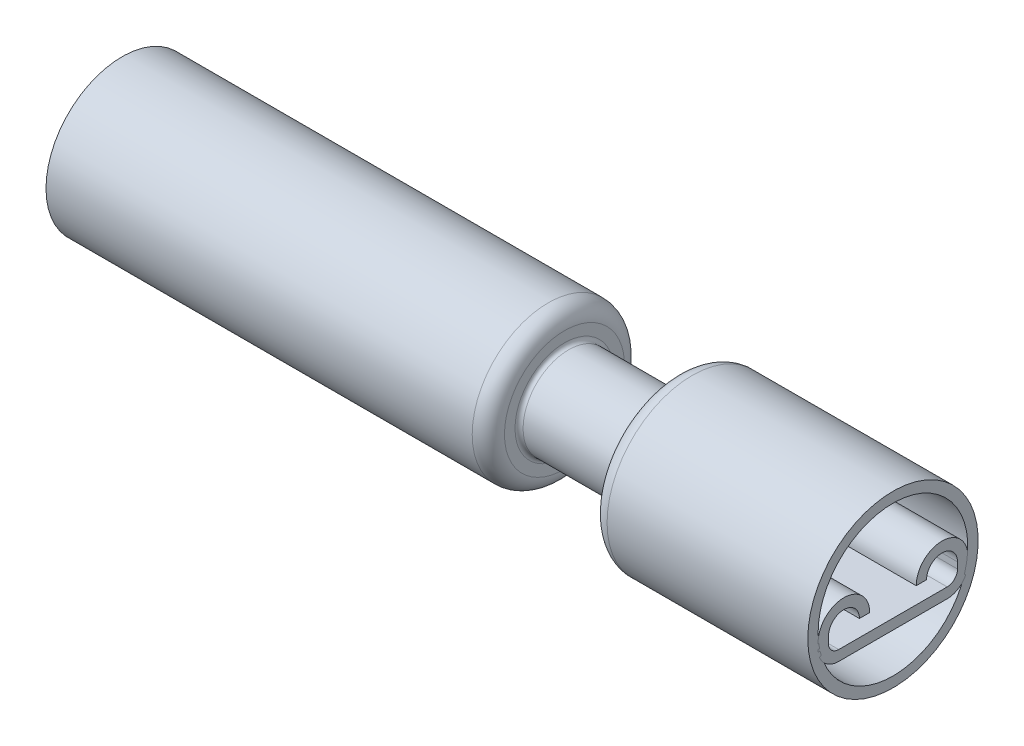
SolidWorks part; units mm, degrees
ref_plane "Front Plane" through (0, 0, 0) normal (0, 0, 1) x (1, 0, 0)
ref_plane "Top Plane" through (0, 0, 0) normal (0, 1, 0) x (1, 0, 0)
ref_plane "Right Plane" through (0, 0, 0) normal (1, 0, 0) x (0, 0, -1)
sketch "Sketch1" plane through (0, 0, 0) normal (1, 0, 0) x (0, 0, -1)
  line L0 (0, 3.2385) -> (0, -3.2385) construction
  line L1 (2.667, -1.7272) -> (-2.667, -1.7272) construction
  line L2 (-3.683, -0.7112) -> (-3.683, -0.4064) construction
  line L3 (-0.6096, 1.0559) -> (0, 0) construction
  line L4 (3.683, -0.7112) -> (3.683, -0.4064) construction
  line L5 (-3.175, -0.7112) -> (-3.175, -0.4064) construction
  line L6 (2.667, -1.2192) -> (-2.667, -1.2192) construction
  line L7 (3.175, -0.7112) -> (3.175, -0.4064) construction
  line L8 (-1.143, -0.4064) -> (-1.651, -0.4064) construction
  line L9 (1.143, -0.4064) -> (1.651, -0.4064) construction
  arc A0 (-3.683, -0.4064) -> (-1.143, -0.4064) centre (-2.413, -0.4064) cw construction
  arc A1 (-2.667, -1.7272) -> (-3.683, -0.7112) centre (-2.667, -0.7112) cw construction
  arc A2 (2.667, -1.7272) -> (3.683, -0.7112) centre (2.667, -0.7112) ccw construction
  arc A3 (3.683, -0.4064) -> (1.143, -0.4064) centre (2.413, -0.4064) ccw construction
  arc A4 (-3.175, -0.4064) -> (-1.651, -0.4064) centre (-2.413, -0.4064) cw construction
  arc A5 (-2.667, -1.2192) -> (-3.175, -0.7112) centre (-2.667, -0.7112) cw construction
  arc A6 (2.667, -1.2192) -> (3.175, -0.7112) centre (2.667, -0.7112) ccw construction
  arc A7 (3.175, -0.4064) -> (1.651, -0.4064) centre (2.413, -0.4064) ccw construction
  circle A8 centre (0, 0) radius 1.2192 construction
  point P4 (0, 0)
  point P14 (-0.6096, 1.0559)
  dimension "D2" = 1.016
  dimension "D3" = 1.27
  dimension "D4" = 2.4384
  dimension "Tubing ID" = 6.477
  dimension "Tab Width" = 6.35
  dimension "D5" = 30
  dimension "Tab Thickness" = 0.8128
  dimension "Thickness" = 0.508
sketch "Sketch2" plane through (0, 0, 0) normal (0, 0, 1) x (1, 0, 0)
  line L0 (18.9611, 0) -> (-18.9611, 0) construction
  point P4 (0, 0)
  dimension "Length" = 37.9222
sketch "Sketch3" plane through (0, 0, 0) normal (0, 1, 0) x (1, 0, 0)
  line L0 (8.8011, 0) -> (18.9611, 0) construction
  line L1 (18.9611, 0) -> (-18.9611, 0) construction
  line L2 (18.9611, -3.683) -> (18.9611, 3.683)
  line L3 (18.9611, 3.683) -> (11.0236, 3.683)
  line L4 (9.7358, 3.0238) -> (8.8011, 1.7272)
  line L5 (0, -1.2192) -> (0, 1.2192) construction
  line L6 (8.8011, 1.7272) -> (8.8011, -1.7272)
  line L7 (0, -1.2192) -> (0, 1.2192) construction
  line L8 (9.7358, -3.0238) -> (8.8011, -1.7272)
  line L9 (18.9611, -3.683) -> (11.0236, -3.683)
  arc A0 (11.0236, 3.683) -> (9.7358, 3.0238) centre (11.0236, 2.0955) ccw
  arc A1 (9.7358, -3.0238) -> (11.0236, -3.683) centre (11.0236, -2.0955) ccw
  point P21 (10.211, 3.683)
  point P24 (10.211, -3.683)
  dimension "D4" = 1.5875
  dimension "D1" = 10.16
  dimension "D2" = 0.508
  dimension "D3" = 7.9375
extrude "Boss-Extrude1" add sketch "Sketch3" along normal up to vertex (-0.4064 mm away) from vertex up to point (0, -0.4064, 3.683) starting at point (0, -1.7272, 2.667)
fillet "Fillet1" radius 1.016 6 edges at (14.9923, -1.7272, 3.683) (9.2685, -1.7272, 2.3755) (10.3003, -1.7272, 3.5086) (9.2685, -1.7272, -2.3755) (10.3003, -1.7272, -3.5086) (14.9923, -1.7272, -3.683)
shell "Shell1" thickness 0.508 removed face at (12.1105, -0.4064, 0) removed face at (18.9611, -1.0184, 0) removed face at (8.8011, -0.8758, 0)
sketch "Sketch4" plane through (8.8011, 0, 0) normal (-1, 0, 0) x (0, 0, 1)
  circle A0 centre (0, 0) radius 1.2192 construction
  circle A1 centre (0, 0) radius 1.2192
  circle A2 centre (0, 0) radius 1.7272
extrude "Boss-Extrude2" add sketch "Sketch4" along normal offset from surface (6.5087 mm away) 16.6687 up to face at (18.9611, -0.9162, 0)
sketch "Sketch5" plane through (2.2923, 0, 0) normal (-1, 0, 0) x (0, 0, 1)
  circle A0 centre (0, 0) radius 1.2192 construction
  circle A1 centre (0, 0) radius 1.2192
extrude "Cut-Extrude1" cut sketch "Sketch5" against normal through all
sketch "Sketch6" plane through (18.9611, 0, 0) normal (1, 0, 0) x (0, 0, -1)
  line L0 (-1.143, -0.4064) -> (-1.651, -0.4064) construction
  line L1 (-3.175, -0.7112) -> (-3.175, -0.4064) construction
  line L2 (2.667, -1.2192) -> (-2.667, -1.2192) construction
  line L3 (3.175, -0.7112) -> (3.175, -0.4064) construction
  line L4 (1.143, -0.4064) -> (1.651, -0.4064) construction
  line L5 (3.683, -0.7112) -> (3.683, -0.4064) construction
  line L6 (2.667, -1.7272) -> (-2.667, -1.7272) construction
  line L7 (-3.683, -0.7112) -> (-3.683, -0.4064) construction
  line L8 (3.683, -0.4064) -> (3.175, -0.4064)
  line L14 (-2.667, -1.7272) -> (2.667, -1.7272)
  line L16 (3.683, -0.4064) -> (3.175, -0.4064)
  line L22 (-2.667, -1.7272) -> (2.667, -1.7272)
  line L24 (-1.143, -0.4064) -> (-1.651, -0.4064)
  line L25 (-3.175, -0.7112) -> (-3.175, -0.4064)
  line L26 (2.667, -1.2192) -> (-2.667, -1.2192)
  line L27 (3.175, -0.7112) -> (3.175, -0.4064)
  line L28 (1.143, -0.4064) -> (1.651, -0.4064)
  line L29 (3.683, -0.7112) -> (3.683, -0.4064)
  line L30 (2.667, -1.7272) -> (-2.667, -1.7272)
  line L31 (-3.683, -0.7112) -> (-3.683, -0.4064)
  line L34 (3.175, -0.4064) -> (3.175, -0.7112)
  line L35 (3.175, -0.4064) -> (3.175, -0.7112)
  line L36 (2.667, -1.2192) -> (-2.667, -1.2192)
  line L37 (2.667, -1.2192) -> (-2.667, -1.2192)
  line L38 (-3.175, -0.7112) -> (-3.175, -0.4064)
  line L39 (-3.175, -0.7112) -> (-3.175, -0.4064)
  line L40 (-3.175, -0.4064) -> (-3.683, -0.4064)
  line L41 (-3.175, -0.4064) -> (-3.683, -0.4064)
  line L42 (-3.683, -0.4064) -> (-3.683, -0.7112)
  line L43 (-3.683, -0.4064) -> (-3.683, -0.7112)
  line L44 (3.683, -0.7112) -> (3.683, -0.4064)
  line L45 (3.683, -0.7112) -> (3.683, -0.4064)
  arc A0 (-1.143, -0.4064) -> (-3.683, -0.4064) centre (-2.413, -0.4064) ccw construction
  arc A1 (-1.651, -0.4064) -> (-3.175, -0.4064) centre (-2.413, -0.4064) ccw construction
  arc A2 (-3.175, -0.7112) -> (-2.667, -1.2192) centre (-2.667, -0.7112) ccw construction
  arc A3 (2.667, -1.2192) -> (3.175, -0.7112) centre (2.667, -0.7112) ccw construction
  arc A6 (-3.683, -0.7112) -> (-2.667, -1.7272) centre (-2.667, -0.7112) ccw
  arc A7 (2.667, -1.7272) -> (3.683, -0.7112) centre (2.667, -0.7112) ccw
  arc A10 (-3.683, -0.7112) -> (-2.667, -1.7272) centre (-2.667, -0.7112) ccw
  arc A11 (2.667, -1.7272) -> (3.683, -0.7112) centre (2.667, -0.7112) ccw
  arc A12 (3.175, -0.4064) -> (1.651, -0.4064) centre (2.413, -0.4064) ccw construction
  arc A13 (3.683, -0.4064) -> (1.143, -0.4064) centre (2.413, -0.4064) ccw construction
  arc A14 (2.667, -1.7272) -> (3.683, -0.7112) centre (2.667, -0.7112) ccw construction
  arc A15 (-3.683, -0.7112) -> (-2.667, -1.7272) centre (-2.667, -0.7112) ccw construction
  arc A16 (-1.143, -0.4064) -> (-3.683, -0.4064) centre (-2.413, -0.4064) ccw
  arc A17 (-1.651, -0.4064) -> (-3.175, -0.4064) centre (-2.413, -0.4064) ccw
  arc A18 (-3.175, -0.7112) -> (-2.667, -1.2192) centre (-2.667, -0.7112) ccw
  arc A19 (2.667, -1.2192) -> (3.175, -0.7112) centre (2.667, -0.7112) ccw
  arc A20 (3.175, -0.4064) -> (1.651, -0.4064) centre (2.413, -0.4064) ccw
  arc A21 (3.683, -0.4064) -> (1.143, -0.4064) centre (2.413, -0.4064) ccw
  arc A22 (2.667, -1.7272) -> (3.683, -0.7112) centre (2.667, -0.7112) ccw
  arc A23 (-3.683, -0.7112) -> (-2.667, -1.7272) centre (-2.667, -0.7112) ccw
  arc A26 (2.667, -1.2192) -> (3.175, -0.7112) centre (2.667, -0.7112) ccw
  arc A27 (2.667, -1.2192) -> (3.175, -0.7112) centre (2.667, -0.7112) ccw
  arc A28 (-3.175, -0.7112) -> (-2.667, -1.2192) centre (-2.667, -0.7112) ccw
  arc A29 (-3.175, -0.7112) -> (-2.667, -1.2192) centre (-2.667, -0.7112) ccw
  line M13 (3.683, -0.4064) -> (3.175, -0.4064)
  line M14 (3.175, -0.4064) -> (3.175, -0.7112)
  arc M15 (3.175, -0.7112) -> (2.667, -1.2192) centre (2.667, -0.7112) cw
  line M16 (2.667, -1.2192) -> (-2.667, -1.2192)
  arc M17 (-2.667, -1.2192) -> (-3.175, -0.7112) centre (-2.667, -0.7112) cw
  line M18 (-3.175, -0.7112) -> (-3.175, -0.4064)
  line M19 (-3.175, -0.4064) -> (-3.683, -0.4064)
  line M20 (-3.683, -0.4064) -> (-3.683, -0.7112)
  arc M21 (-3.683, -0.7112) -> (-2.667, -1.7272) centre (-2.667, -0.7112) ccw
  line M22 (-2.667, -1.7272) -> (2.667, -1.7272)
  arc M23 (2.667, -1.7272) -> (3.683, -0.7112) centre (2.667, -0.7112) ccw
  line M24 (3.683, -0.7112) -> (3.683, -0.4064)
  dimension "D1" = 0
extrude "Boss-Extrude3" add sketch "Sketch6" against normal up to vertex (7.9375 mm away) contours A17 L24 A16 L31 L25 M19 | L29 A21 L28 A20 L27 M13 | M24 M13 M14 M15 M16 M17 M18 M19 M20 M21 M22 M23 region at (18.9611, -1.332, 0) region at (18.9611, -0.378, -3.429) region at (18.9611, 0.8352, 2.413) up to point (11.0236, -0.4064, -3.175)
sketch "Sketch9" plane through (0, 0, 0) normal (0, 0, 1) x (1, 0, 0)
  line L1 (-18.9611, 3.2385) -> (2.2923, 3.2385)
  line L2 (8.8011, 1.7272) -> (2.2923, 1.7272)
  line L9 (-18.9611, 0) -> (11.0236, 0) construction
  line L10 (11.0236, 0.8636) -> (11.0236, -0.4064) construction
  line L14 (18.9611, -0.4064) -> (18.9611, 0.8636) construction
  line L15 (8.8011, 3.9171) -> (8.8011, 2.6473) construction
  line L17 (2.2923, 3.2385) -> (2.2923, 1.7272)
  line L20 (18.9611, 3.683) -> (8.8011, 3.683)
  line L21 (8.8011, 3.683) -> (8.8011, 1.7272)
  line L22 (-18.9611, 3.7465) -> (2.8003, 3.7465)
  line L24 (8.2931, 2.2352) -> (2.8003, 2.2352)
  line L25 (8.2931, 4.191) -> (8.2931, 2.2352)
  line L26 (18.9611, 4.191) -> (8.2931, 4.191)
  line L27 (-18.9611, 3.2385) -> (-18.9611, 3.7465)
  line L28 (18.9611, 3.683) -> (18.9611, 4.191)
  line L29 (18.9611, 3.683) -> (9.0116, 3.683) construction
  line L30 (1.2702, 2.9748) -> (1.7406, 2.3056) construction
  line L31 (1.2046, 2.1848) -> (1.4171, 1.8825) construction
  line L32 (12.3815, 1.7272) -> (3.8524, 1.7272) construction
  line L33 (2.8003, 2.2352) -> (2.8003, 3.7465)
  line L34 (8.8011, -0.4064) -> (8.8011, 1.7272) construction
  line L35 (18.9611, 4.191) -> (9.2813, 4.191) construction
  line L36 (2.2923, 3.2385) -> (2.8003, 3.2385) construction
  line L37 (8.2931, 4.3899) -> (8.2931, 2.2352) construction
  line L38 (-18.9611, 3.7465) -> (2.4782, 3.7465) construction
  line L39 (8.2931, 2.2352) -> (3.1556, 2.2352) construction
  line L40 (-18.9611, 3.2385) -> (2.2923, 3.2385) construction
  arc A8 (2.2923, 3.2385) -> (1.7406, 2.3056) centre (1.8695, 2.859) cw construction
  arc A9 (3.1556, 2.2352) -> (1.2046, 2.1848) centre (2.196, 1.5949) cw construction
  arc A10 (8.2931, 2.2352) -> (8.2931, 2.2352) centre (8.2931, 2.2352) ccw construction
  arc A11 (9.0116, 3.683) -> (8.8011, 3.9171) centre (8.6403, 3.5609) ccw construction
  arc A12 (3.8524, 1.7272) -> (1.2702, 2.9748) centre (2.196, 1.5949) cw construction
  arc A13 (2.4782, 3.7465) -> (1.4171, 1.8825) centre (1.8695, 2.859) cw construction
  arc A14 (9.2813, 4.191) -> (8.2931, 4.3899) centre (8.6403, 3.5609) ccw construction
  arc A15 (12.3815, 1.7272) -> (8.8011, 2.6473) centre (10.6966, 2.5972) ccw construction
  point P68 (2.2923, 1.7272)
  dimension "D2" = 7.366
  dimension "D4" = 0.508
revolve "Revolve1" add sketch "Sketch9" angle 360 about L9
fillet "Fillet2" radius 0.7937 2 edges at (8.2931, 0, 4.191) (2.8003, 0, 3.7465)
fillet "Fillet3" radius 0.1984 2 edges at (2.8003, 0, 2.2352) (8.2931, 0, 2.2352)
equation "\"D2@Sketch3\" = \"Thickness@Sketch1\""
equation "\"D1@Boss-Extrude1\"=\"Tab Thickness@Sketch1\"/2"
equation "\"D1@Fillet1\"=\"D2@Sketch1\""
equation "\"D1@Shell1\" = \"Thickness@Sketch1\""
equation "\"D1@Sketch4\" = \"Thickness@Sketch1\""
equation "\"D2@Sketch9\" = \"Tab Width@Sketch1\" +  ( 2 * \"Thickness@Sketch1\" ) "
equation "\"D4@Sketch9\" = \"Thickness@Sketch1\""
